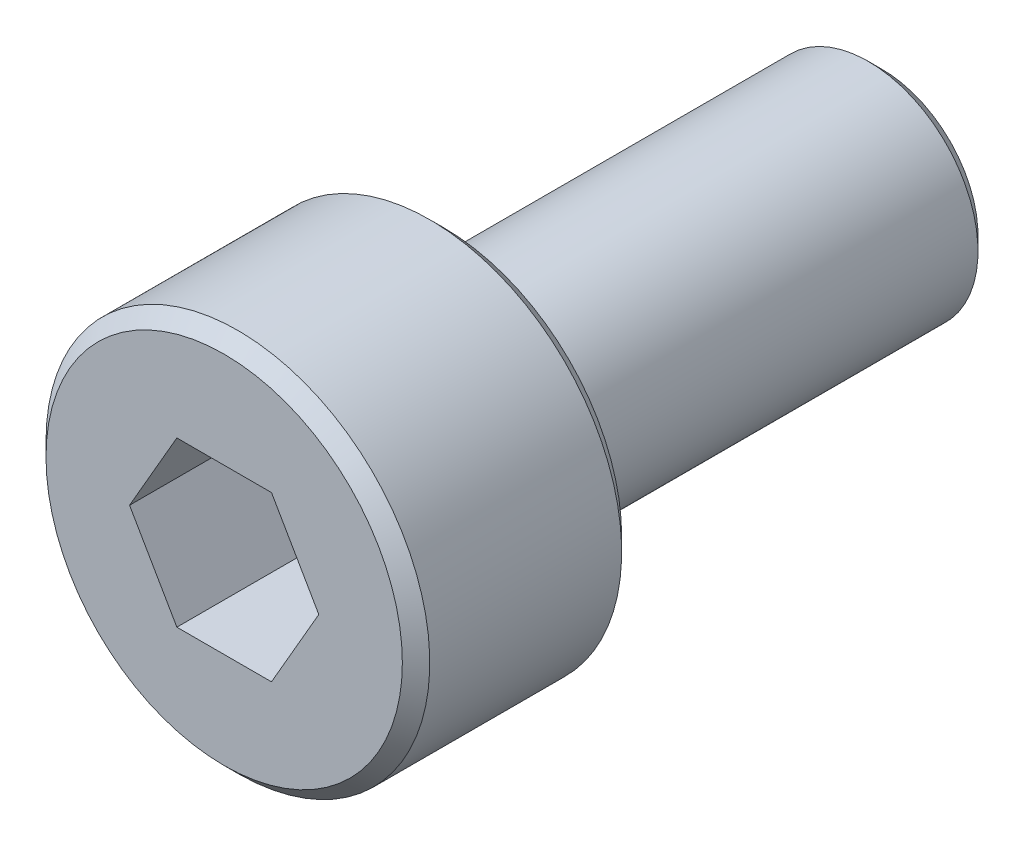
SolidWorks part; units mm, degrees
ref_plane "Front Plane" through (0, 0, 0) normal (0, 0, 1) x (1, 0, 0)
ref_plane "Top Plane" through (0, 0, 0) normal (0, 1, 0) x (1, 0, 0)
ref_plane "Right Plane" through (0, 0, 0) normal (1, 0, 0) x (0, 0, -1)
ref_plane "Plane1" through (0, 0, 4) normal (0, 0, 1) x (1, 0, 0)
sketch "Sketch1" plane through (0, 0, 4) normal (0, 0, 1) x (1, 0, 0)
  circle A0 centre (0, 0) radius 3.5
extrude "Boss-Extrude1" add sketch "Sketch1" against normal blind 4
sketch "Sketch2" plane through (0, 0, 0) normal (0, 0, -1) x (-1, 0, 0)
  circle A0 centre (0, 0) radius 2
extrude "Boss-Extrude2" add sketch "Sketch2" along normal blind 8
sketch "Sketch3" plane through (0, 0, 4) normal (0, 0, 1) x (1, 0, 0)
  line L0 (-1.726, 0) -> (-0.863, -1.4948)
  line L1 (-0.863, -1.4948) -> (0.863, -1.4948)
  line L2 (0.863, -1.4948) -> (1.726, 0)
  line L3 (1.726, 0) -> (0.863, 1.4948)
  line L4 (0.863, 1.4948) -> (-0.863, 1.4948)
  line L5 (-0.863, 1.4948) -> (-1.726, 0)
extrude "Cut-Extrude1" cut sketch "Sketch3" against normal blind 3
chamfer "Chamfer1" distance 0.25 angle 45 3 edges at (-3.5, 0, 4) (-2, 0, -8) (-3.5, 0, 0)
ref_axis "Axis1" through (0, 0, -10.4264) along (0, 0, 1)
